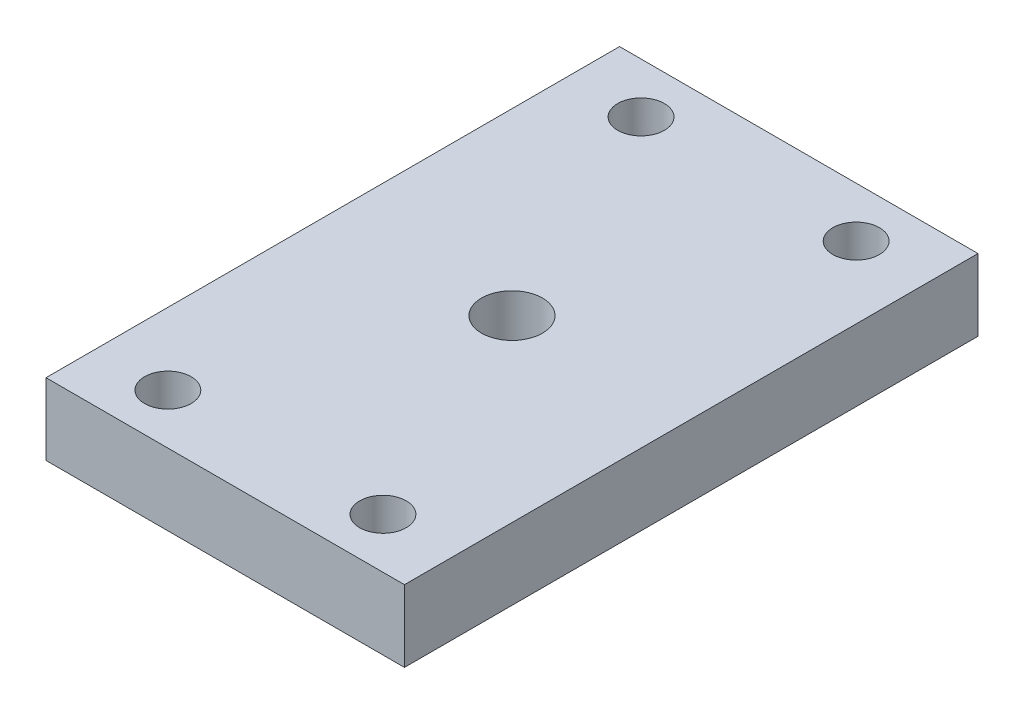
SolidWorks part; units mm, degrees
ref_plane "Front Plane" through (0, 0, 0) normal (0, 0, 1) x (1, 0, 0)
ref_plane "Top Plane" through (0, 0, 0) normal (0, 1, 0) x (1, 0, 0)
ref_plane "Right Plane" through (0, 0, 0) normal (1, 0, 0) x (0, 0, -1)
sketch "Sketch1" plane through (0, 0, 0) normal (0, 1, 0) x (1, 0, 0)
  line L0 (30.8021, -28.7414) -> (-19.1979, -28.7414) construction
  line L5 (-19.0216, -6.7414) -> (30.8021, -6.7414) construction
  line L6 (-19.1097, -46.7414) -> (30.8903, -46.7414)
  line L7 (30.8021, 15.2586) -> (-19.0216, 15.2586) construction
  line L8 (30.8021, 15.2586) -> (30.8021, -28.7414) construction
  line L9 (30.8021, -28.7414) -> (-19.0216, -28.7414) construction
  line L10 (-19.0216, 15.2586) -> (-19.0216, -28.7414) construction
  line L11 (-19.0216, 15.2586) -> (30.8021, -28.7414) construction
  line L12 (-19.0216, -28.7414) -> (30.8021, 15.2586) construction
  line L13 (-19.1097, -46.7414) -> (-19.1097, 33.2586)
  line L14 (-19.1097, 33.2586) -> (30.8903, 33.2586)
  line L15 (30.8903, -46.7414) -> (30.8903, 33.2586)
  line L16 (-19.1097, -46.7414) -> (30.8903, 33.2586) construction
  line L17 (-19.1097, 33.2586) -> (30.8903, -46.7414) construction
  point P0 (0, 0)
  point P1 (5.8903, -6.7414)
  dimension "D1" = 80
  dimension "D2" = 50
extrude "Boss-Extrude1" add sketch "Sketch1" along normal blind 10
sketch "Sketch2" plane through (0, 0, 0) normal (0, -1, 0) x (1, 0, 0)
  line L0 (5.8903, -33.2586) -> (5.8903, 46.7414) construction
  line L1 (30.8903, -33.2586) -> (-19.1097, -33.2586) construction
  line L2 (-19.1097, 46.7414) -> (30.8903, 46.7414) construction
  circle A0 centre (5.8903, 6.7414) radius 4.25
  dimension "D1" = 8.5
extrude "Cut-Extrude1" cut sketch "Sketch2" against normal up to next
sketch "Sketch5" plane through (0, 10, 0) normal (0, 1, 0) x (1, 0, 0)
  line L0 (-19.1097, -39.7414) -> (30.8903, -39.7414) construction
  line L1 (-19.1097, 33.2586) -> (-19.1097, -46.7414) construction
  line L2 (30.8903, -46.7414) -> (30.8903, 33.2586) construction
  line L3 (-19.1097, 26.2586) -> (30.8903, 26.2586) construction
  line L4 (-19.1097, -46.7414) -> (30.8903, -46.7414) construction
  line L5 (30.8903, 33.2586) -> (-19.1097, 33.2586) construction
  circle A0 centre (-9.1097, -39.7414) radius 3.25
  circle A1 centre (20.8903, -39.7414) radius 3.25
  circle A2 centre (-9.1097, 26.2586) radius 3.25
  circle A3 centre (20.8903, 26.2586) radius 3.25
  dimension "D3" = 6.5
  dimension "D4" = 6.5
  dimension "D5" = 6.5
  dimension "D6" = 6.5
  dimension "D1" = 7
  dimension "D2" = 7
  dimension "D7" = 10
  dimension "D8" = 10
  dimension "D9" = 10
  dimension "D10" = 10
extrude "Cut-Extrude3" cut sketch "Sketch5" against normal up to next
sketch "Sketch6" plane through (0, 0, 0) normal (0, 1, 0) x (1, 0, 0)
  line L4 (30.8903, -46.7414) -> (30.8903, 33.2586)
  line L5 (30.8903, 33.2586) -> (-19.1097, 33.2586)
  line L6 (-19.1097, 33.2586) -> (-19.1097, -46.7414)
  line L7 (-19.1097, -46.7414) -> (30.8903, -46.7414)
  line L8 (30.8903, -46.7414) -> (30.8903, 33.2586)
  line L9 (30.8903, 33.2586) -> (-19.1097, 33.2586)
  line L10 (-19.1097, 33.2586) -> (-19.1097, -46.7414)
  line L11 (-19.1097, -46.7414) -> (30.8903, -46.7414)
  circle A0 centre (20.8903, -39.7414) radius 3.25 construction
  circle A1 centre (-9.1097, -39.7414) radius 3.25 construction
  circle A2 centre (5.8903, -6.7414) radius 4.25 construction
  circle A3 centre (20.8903, 26.2586) radius 3.25 construction
  circle A4 centre (-9.1097, 26.2586) radius 3.25 construction
  circle A5 centre (20.8903, -39.7414) radius 3.25
  circle A6 centre (-9.1097, -39.7414) radius 3.25
  circle A7 centre (5.8903, -6.7414) radius 4.25
  circle A8 centre (20.8903, 26.2586) radius 3.25
  circle A9 centre (-9.1097, 26.2586) radius 3.25
  dimension "D1" = 0
